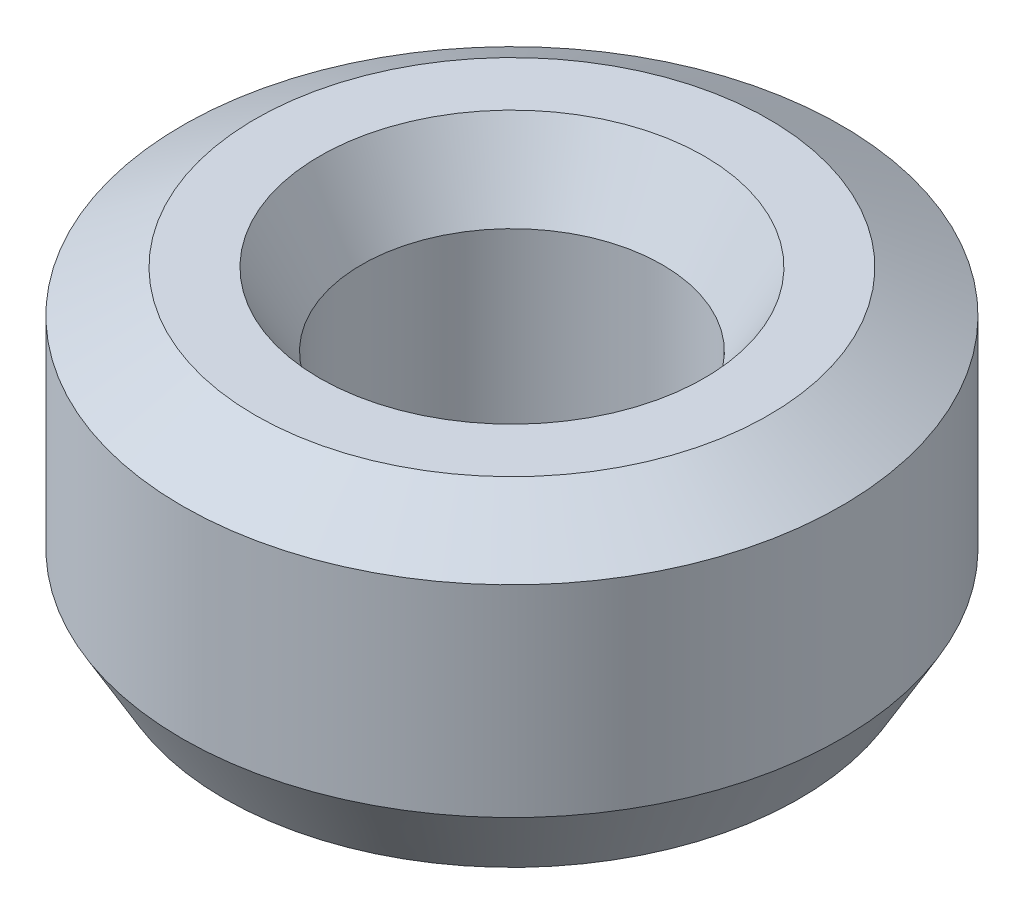
SolidWorks part; units mm, degrees
ref_plane "Front Plane" through (0, 0, 0) normal (0, 0, 1) x (1, 0, 0)
ref_plane "Top Plane" through (0, 0, 0) normal (0, 1, 0) x (1, 0, 0)
ref_plane "Right Plane" through (0, 0, 0) normal (1, 0, 0) x (0, 0, -1)
sketch "Sketch1" plane through (0, 0, 0) normal (0, 1, 0) x (1, 0, 0)
  circle A0 centre (0, 0) radius 27.5
  dimension "SLEEVE_OD" = 55
extrude "Boss-Extrude1" add sketch "Sketch1" along normal blind 26.4167
sketch "Sketch2" plane through (0, 0, 0) normal (0, 1, 0) x (1, 0, 0)
  circle A0 centre (0, 0) radius 12.537
  dimension "BORE_D" = 25.0739
extrude "Cut-Extrude1" cut sketch "Sketch2" along normal through all
chamfer "Chamfer1" distance 3.5129 angle 60 4 edges at (0, 26.4167, 12.537) (0, 0, 12.537) (0, 0, 27.5) (0, 26.4167, 27.5) first distance on face at (0, 26.4167, 12.537) first distance on face at (0, 0, 12.537) first distance on face at (0, 26.4167, 27.5)
